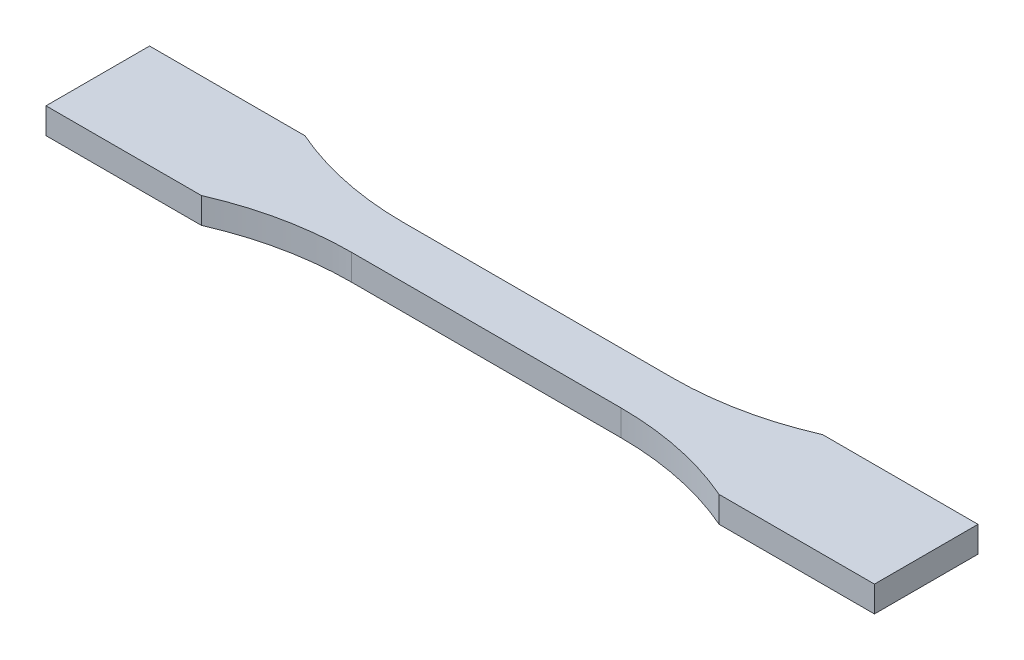
SolidWorks part; units mm, degrees
material "PET"
ref_plane "Front Plane" through (0, 0, 0) normal (0, 0, 1) x (1, 0, 0)
ref_plane "Top Plane" through (0, 0, 0) normal (0, 1, 0) x (1, 0, 0)
ref_plane "Right Plane" through (0, 0, 0) normal (1, 0, 0) x (0, 0, -1)
sketch "Sketch1" plane through (0, 0, 0) normal (0, 1, 0) x (1, 0, 0)
  line L0 (0, -6.35) -> (0, 6.35) construction
  line L1 (-63.5, 6.35) -> (63.5, 6.35)
  line L2 (-63.5, -6.35) -> (63.5, -6.35)
  line L3 (-63.5, 6.35) -> (-63.5, -6.35) construction
  line L4 (-63.5, 6.35) -> (-63.5, -6.35) construction
  line L5 (-63.5, 12.7) -> (-101.6, 12.7)
  line L6 (-101.6, 12.7) -> (-101.6, -12.7)
  line L7 (-101.6, -12.7) -> (-63.5, -12.7)
  line L9 (-63.5, 0) -> (-101.6, 0) construction
  line L10 (63.5, 6.35) -> (63.5, -6.35) construction
  line L11 (63.5, -12.7) -> (63.5, -6.35)
  line L12 (63.5, 6.35) -> (63.5, 12.7)
  line L13 (63.5, 0) -> (101.6, 0) construction
  line L14 (101.6, -12.7) -> (63.5, -12.7)
  line L15 (101.6, 12.7) -> (101.6, -12.7)
  line L16 (63.5, 12.7) -> (101.6, 12.7)
  line L18 (-63.5, 12.7) -> (-63.5, 6.35)
  line L19 (-63.5, -6.35) -> (-63.5, -12.7)
  dimension "D1" = 203.2
  dimension "D2" = 25.4
  dimension "D3" = 12.7
  dimension "D4" = 127
extrude "1/4 Inch Thickness" add sketch "Sketch1" along normal mid plane 6.35
fillet "Fillet1" radius 76.2 4 edges at (63.5, 0, 6.35) (63.5, 0, -6.35) (-63.5, 0, 6.35) (-63.5, 0, -6.35)
